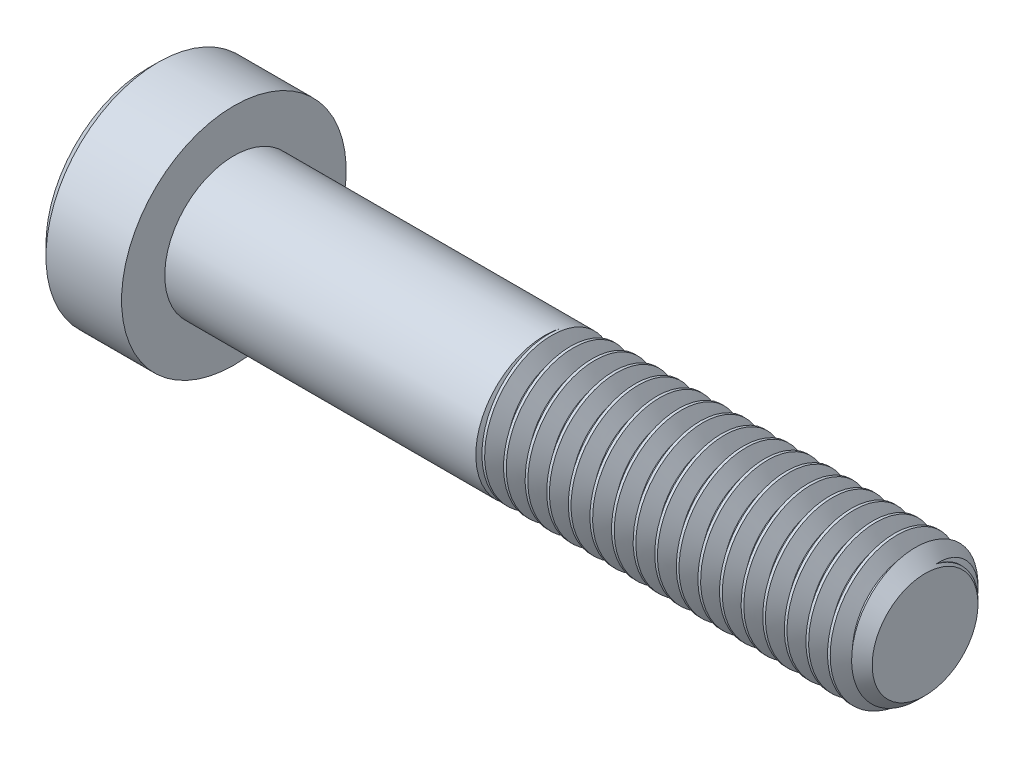
SolidWorks part; units mm, degrees
ref_plane "Front Plane" through (0, 0, 0) normal (0, 0, 1) x (1, 0, 0)
ref_plane "Top Plane" through (0, 0, 0) normal (0, 1, 0) x (1, 0, 0)
ref_plane "Right Plane" through (0, 0, 0) normal (1, 0, 0) x (0, 0, -1)
sketch "Sketch1" plane through (0, 0, 0) normal (0, 0, 1) x (1, 0, 0)
  line L0 (20, 0) -> (-20, 0) construction
  line L1 (20, 4) -> (20, -4) construction
  line L2 (-20, 6.5) -> (-20, -6.5) construction
  line L3 (-20, 6.5) -> (-24.375, 6.5) construction
  line L4 (-24.375, 6.5) -> (-25, 5.875) construction
  line L5 (-25, 5.875) -> (-25, -5.875) construction
  line L6 (-25, -5.875) -> (-24.375, -6.5) construction
  line L7 (-24.375, -6.5) -> (-20, -6.5) construction
  line L8 (-2, 4) -> (-2, -4) construction
  point P7 (-21.05, 0)
  point P12 (15, -4)
  dimension "D1" = 45
  dimension "Dec." = 8
  dimension "Length" = 40
  dimension "Head Dia" = 13
  dimension "Head Height" = 5
  dimension "Hex Depth" = 3.95
  dimension "Chamfer" = 0.625
  dimension "D2" = 5
  dimension "Thread Length" = 22
ref_plane "Plane1" through (20, 0, 0) normal (1, 0, 0) x (0, 0, -1)
ref_plane "Plane2" through (-25, 0, 0) normal (1, 0, 0) x (0, 0, -1)
sketch "Sketch2" plane through (20, 0, 0) normal (1, 0, 0) x (0, 0, -1)
  circle A0 centre (0, 0) radius 4
extrude "Boss-Extrude1" add sketch "Sketch2" against normal up to vertex (22 mm away) up to point (-2, 4, 0)
sketch "Sketch3" plane through (20, 0, 0) normal (1, 0, 0) x (0, 0, -1)
  circle A0 centre (0, 0) radius 4 construction
  circle A1 centre (0, 0) radius 4
curve "Helix/Spiral1" pitch 1.25 height 23.25 radius 4 centre (20, 0, 0) axis (-1, 0, 0) start towards (0, 1, 0) parameters "Pitch"=1.25
chamfer "Chamfer1" distance 0.9375 angle 45 1 edges at (20, 0, -4)
sketch "Sketch5" plane through (0, 0, 0) normal (0, 0, 1) x (1, 0, 0)
  line L0 (19.4531, 4) -> (20.5469, 4)
  line L1 (20.5469, 4) -> (20.0781, 3.1881)
  line L2 (20.0781, 3.1881) -> (19.9219, 3.1881)
  line L3 (19.9219, 3.1881) -> (19.4531, 4)
  line L4 (20, 3.1881) -> (20, 4) construction
  line L5 (19.6875, 3.5941) -> (20.3125, 3.5941) construction
  dimension "D1" = 60
  dimension "D2" = 0.625
  dimension "D3" = 0.1562
sweep "Cut-Sweep1" cut profiles "Sketch5" path "Helix/Spiral1" align with end faces yes
sketch "Sketch4" plane through (-25, 0, 0) normal (1, 0, 0) x (0, 0, -1)
  line L0 (-6.5, 0.7937) -> (6.5, 0.7937) construction
  line L1 (0, 2.8868) -> (-2.5, 1.4434)
  line L2 (-2.5, 1.4434) -> (-2.5, -1.4434)
  line L3 (-2.5, -1.4434) -> (0, -2.8868)
  line L4 (0, -2.8868) -> (2.5, -1.4434)
  line L5 (2.5, -1.4434) -> (2.5, 1.4434)
  line L6 (2.5, 1.4434) -> (0, 2.8868)
  line L7 (0, 0) -> (0, 0.7937) construction
  circle A0 centre (0, 0) radius 2.5 construction
  dimension "Hex Size" = 5
  dimension "D1" = 13
  dimension "D2" = 0.7937
sketch "Sketch10" plane through (0, 0, 0) normal (0, 0, 1) x (1, 0, 0)
  line L0 (-20, 0) -> (0.3094, 0) construction
  line L1 (0.3094, 0) -> (-2, 4)
  line L2 (-2, 4) -> (-20, 4)
  line L3 (-20, 4) -> (-20, 0)
  line L4 (-20, 6.5) -> (-20, -6.5) construction
  line L5 (-20, 0) -> (0.3094, 0)
  dimension "D1" = 60
revolve "Revolve2" add sketch "Sketch10" angle 360 about L0
sketch "Sketch6" plane through (0, 0, 0) normal (0, 0, 1) x (1, 0, 0)
  line L0 (-24.375, 6.5) -> (-25, 5.875) construction
  line L1 (-20, 6.5) -> (-24.375, 6.5) construction
  line L2 (-20, 6.5) -> (-20, -6.5) construction
  line L3 (-25, 5.875) -> (-25, -5.875) construction
  line L4 (-24.375, 6.5) -> (-25, 5.875)
  line L5 (-20, 6.5) -> (-24.375, 6.5)
  line L6 (-20, 6.5) -> (-20, 0)
  line L7 (-25, 5.875) -> (-25, 0)
  line L8 (-20, 0) -> (-25, 0) construction
  line L9 (-20, 0) -> (-25, 0)
revolve "Revolve1" add sketch "Sketch6" angle 360 about L8
extrude "Cut-Extrude1" cut sketch "Sketch4" along normal up to vertex (3.95 mm away) up to point (-21.05, 0, 0)
sketch "Sketch8" plane through (-25, 0, 0) normal (-1, 0, 0) x (0, 0, 1)
  circle A1 centre (0, 0) radius 2.8868
extrude "Cut-Extrude2" cut sketch "Sketch8" against normal through all draft 45
equation "\"D3@Helix/Spiral1\" = \"Thread Length@Sketch1\"+\"Pitch@Helix/Spiral1\""
equation "\"D3@Sketch5\" = \"Pitch@Helix/Spiral1\"*.125"
equation "\"D2@Sketch5\" = \"Pitch@Helix/Spiral1\"*.50"
equation "\"D1@Chamfer1\" = \"Pitch@Helix/Spiral1\"*.75"
equation "\"D2@Sketch1\" = \"Pitch@Helix/Spiral1\"*4"
equation "\"D1@Sketch4\" = \"Head Dia@Sketch1\""
equation "\"Chamfer@Sketch1\" = \"Head Height@Sketch1\"/8"
